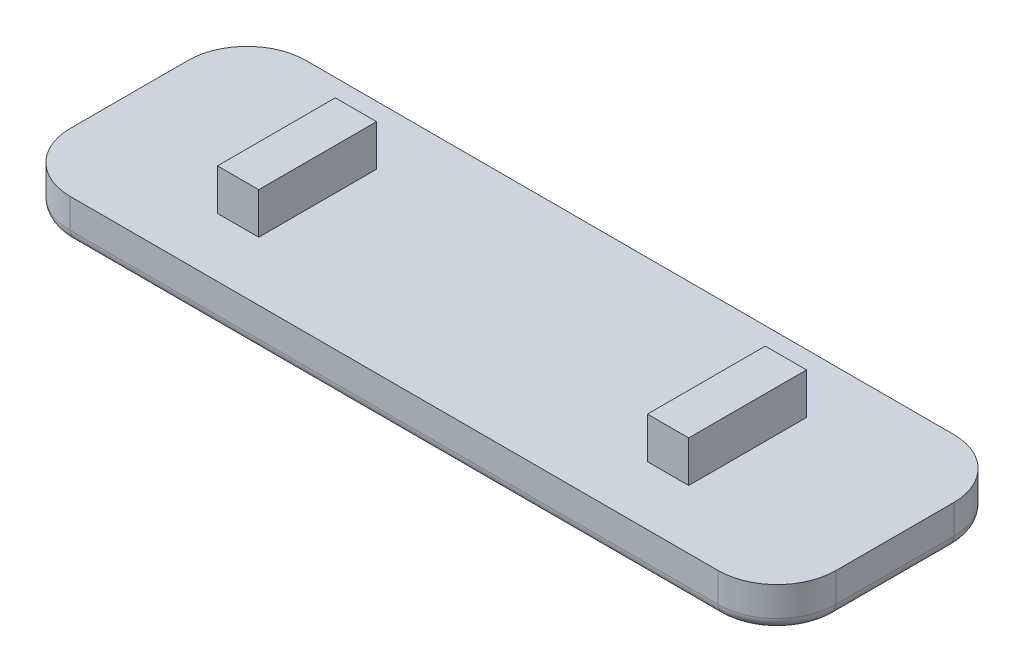
SolidWorks part; units mm, degrees
ref_plane "Front Plane" through (0, 0, 0) normal (0, 0, 1) x (1, 0, 0)
ref_plane "Top Plane" through (0, 0, 0) normal (0, 1, 0) x (1, 0, 0)
ref_plane "Right Plane" through (0, 0, 0) normal (1, 0, 0) x (0, 0, -1)
sketch "Sketch1" plane through (0, 0, 0) normal (0, 0, 1) x (1, 0, 0)
  line L0 (0, 0) -> (0, 10.0808) construction
  line L1 (-82.55, 4.445) -> (82.55, 4.445)
  line L2 (-82.55, 4.445) -> (-82.55, -4.445)
  line L3 (-82.55, -4.445) -> (82.55, -4.445)
  line L4 (82.55, 4.445) -> (82.55, -4.445)
  line L5 (-82.55, 4.445) -> (82.55, -4.445) construction
  line L6 (-82.55, -4.445) -> (82.55, 4.445) construction
  line L7 (-50.8, 4.445) -> (-41.91, 4.445)
  line L8 (-50.8, 4.445) -> (-50.8, 13.335)
  line L9 (-50.8, 13.335) -> (-41.91, 13.335)
  line L10 (-41.91, 4.445) -> (-41.91, 13.335)
  line L11 (50.8, 4.445) -> (50.8, 13.335)
  line L12 (50.8, 13.335) -> (41.91, 13.335)
  line L13 (41.91, 4.445) -> (41.91, 13.335)
  point P0 (0, 0)
  dimension "D1" = 165.1
  dimension "D2" = 8.89
  dimension "D3" = 31.75
  dimension "D4" = 8.89
  dimension "D5" = 8.89
  dimension "D6" = 101.6
extrude "Boss-Extrude1" add sketch "Sketch1" along normal blind 25.4 contours L4 L1 L2 L3 | L13 L1 L11 L12 | L1 L10 L9 L8 region at (0, 0, 0) region at (-46.355, 8.89, 0) region at (46.355, 8.89, 0)
sketch "Sketch2" plane through (0, 0, 25.4) normal (0, 0, 1) x (1, 0, 0)
  line L1 (-82.55, 4.445) -> (82.55, 4.445)
  line L2 (-82.55, 4.445) -> (-82.55, -4.445)
  line L3 (-82.55, -4.445) -> (82.55, -4.445)
  line L4 (82.55, 4.445) -> (82.55, -4.445)
extrude "Boss-Extrude2" add sketch "Sketch2" along normal blind 12.7
sketch "Sketch3" plane through (0, 0, 0) normal (0, 0, -1) x (-1, 0, 0)
  line L1 (-82.55, 4.445) -> (82.55, 4.445)
  line L2 (-82.55, 4.445) -> (-82.55, -4.445)
  line L3 (-82.55, -4.445) -> (82.55, -4.445)
  line L4 (82.55, 4.445) -> (82.55, -4.445)
extrude "Boss-Extrude3" add sketch "Sketch3" along normal blind 12.7
fillet "Fillet1" radius 12.7 4 edges at (82.55, 0, 38.1) (-82.55, 0, 38.1) (-82.55, 0, -12.7) (82.55, 0, -12.7)
fillet "Fillet2" radius 2.54 8 edges at (0, -4.445, -12.7) (-78.8303, -4.445, -8.9803) (-82.55, -4.445, 12.7) (-78.8303, -4.445, 34.3803) (0, -4.445, 38.1) (78.8303, -4.445, 34.3803) (82.55, -4.445, 12.7) (78.8303, -4.445, -8.9803)
